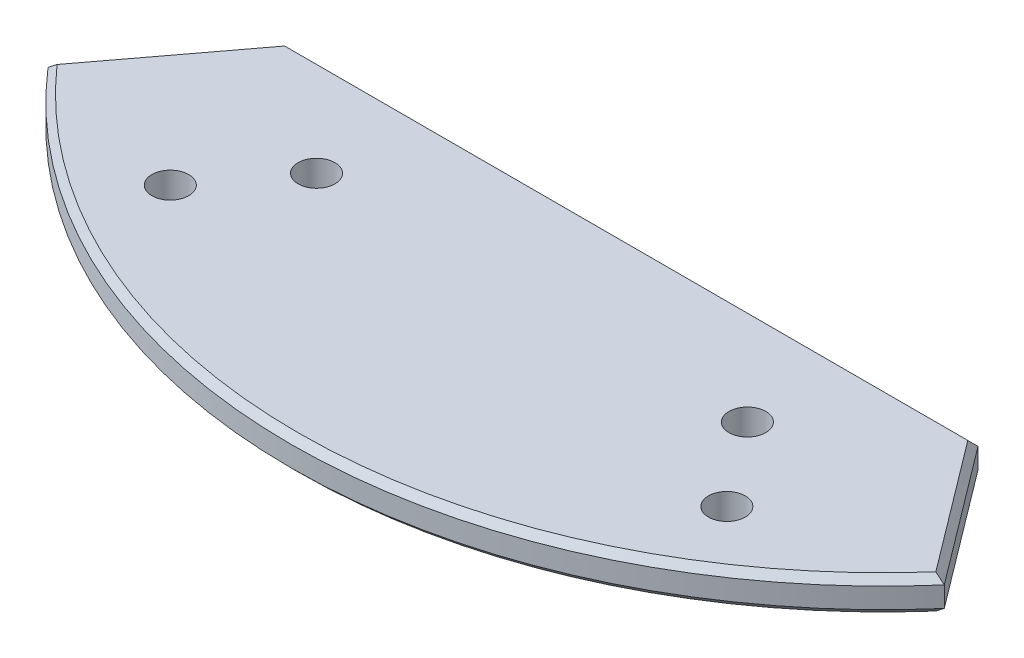
SolidWorks part; units mm, degrees
ref_plane "Front Plane" through (0, 0, 0) normal (0, 0, 1) x (1, 0, 0)
ref_plane "Top Plane" through (0, 0, 0) normal (0, 1, 0) x (1, 0, 0)
ref_plane "Right Plane" through (0, 0, 0) normal (1, 0, 0) x (0, 0, -1)
ref_plane "Plane1" through (0, 36, 0) normal (0, 1, 0) x (1, 0, 0)
sketch "Sketch1" plane through (0, 36, 0) normal (0, 1, 0) x (1, 0, 0)
  line L0 (-60.898, -44.2583) -> (60.898, -44.2583)
  line L5 (60.898, -44.2583) -> (79.1117, -68.4287)
  line L6 (-60.898, -44.2583) -> (-79.1117, -68.4287)
  line L7 (-17.57, 13.2399) -> (-89.16, -81.7632) construction
  line L8 (17.57, 13.2399) -> (89.16, -81.7632) construction
  line L11 (21.4932, -33.5073) -> (57.3512, -81.0925) construction
  line L12 (29.8934, -95.8518) -> (40.9559, -4.9862) construction
  line L13 (0, -1028.2188) -> (0, 48971.7812) construction
  arc A0 (-79.1117, -68.4287) -> (79.1117, -68.4287) centre (0, 0) ccw
  arc A1 (-79.1117, -68.4287) -> (-22, -102.2603) centre (0, 0) ccw construction
  circle A2 centre (38.0319, -62.1015) radius 4 construction
  circle A3 centre (49.1258, -76.8236) radius 4 construction
  arc A5 (-79.1117, -68.4287) -> (79.1117, -68.4287) centre (0, 78.0379) ccw construction
  circle A6 centre (38.0319, -62.1015) radius 3.25
  circle A7 centre (49.1258, -76.8236) radius 3.25
  circle A8 centre (-49.1258, -76.8236) radius 3.25
  circle A9 centre (-38.0319, -62.1015) radius 3.25
  dimension "D1" = 8
  dimension "D2" = 6.5
extrude "Boss-Extrude1" add sketch "Sketch1" along normal blind 6
sketch "Sketch2" plane through (0, 36, 0) normal (0, -1, 0) x (1, 0, 0)
  circle A0 centre (0, 91.2988) radius 4
  circle A1 centre (0, 67.7786) radius 4
  circle A2 centre (0, 44.2583) radius 4
  dimension "D1" = 8
extrude "Cut-Extrude1" cut sketch "Sketch2" against normal blind 4
chamfer "Chamfer1" distance 1.2 angle 45 5 edges at (32.449, 36, 44.2583) (70.0049, 36, 56.3435) (-32.449, 36, 44.2583) (-70.0049, 36, 56.3435) (0, 36, 104.6)
chamfer "Chamfer2" distance 1.2 angle 45 4 edges at (70.0049, 42, 56.3435) (0, 42, 104.6) (-70.0049, 42, 56.3435) (0, 42, 44.2583)
